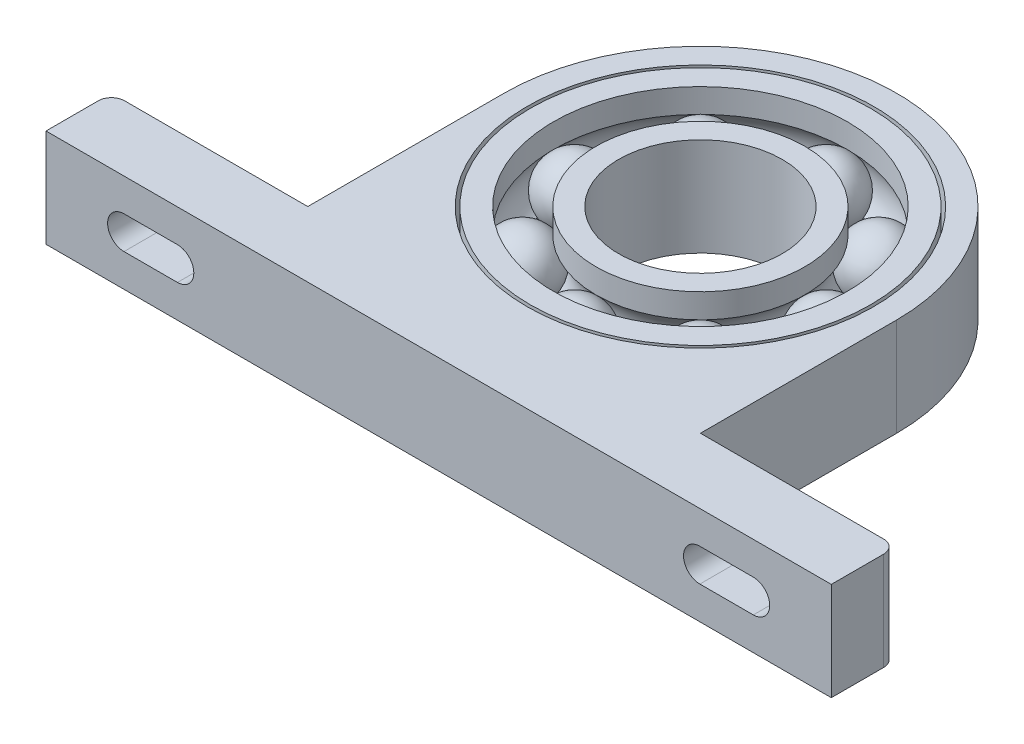
SolidWorks part; units mm, degrees
ref_plane "Front Plane" through (0, 0, 0) normal (0, 0, 1) x (1, 0, 0)
ref_plane "Top Plane" through (0, 0, 0) normal (0, 1, 0) x (1, 0, 0)
ref_plane "Right Plane" through (0, 0, 0) normal (1, 0, 0) x (0, 0, -1)
sketch "Sketch1" plane through (0, 0, 0) normal (0, 0, 1) x (1, 0, 0)
  line L0 (-19.2289, -5) -> (-19.2289, 5)
  line L1 (-15.9578, 7.5) -> (-12.5, 7.5)
  line L2 (-15.9578, 7.5) -> (-15.9578, 3.7815)
  line L3 (-15.9578, -7.5) -> (-12.5, -7.5)
  line L4 (-12.5, 7.5) -> (-12.5, -7.5)
  line L5 (-15.9578, 7.5) -> (-12.5, -7.5) construction
  line L6 (-15.9578, -7.5) -> (-12.5, 7.5) construction
  line L7 (-26, 7.5) -> (-22.4578, 7.5)
  line L8 (-26, 7.5) -> (-26, -7.5)
  line L9 (-26, -7.5) -> (-22.4578, -7.5)
  line L10 (-22.4578, 7.5) -> (-22.4578, 3.8176)
  line L11 (-26, 7.5) -> (-22.4578, -7.5) construction
  line L12 (-26, -7.5) -> (-22.4578, 7.5) construction
  line L13 (0, -10.6091) -> (0, 6.8222) construction
  line L15 (-22.4578, -3.8176) -> (-22.4578, -7.5)
  line L16 (-15.9578, -3.7815) -> (-15.9578, -7.5)
  arc A0 (-22.4578, 3.8176) -> (-22.4578, -3.8176) centre (-19.2289, 0) ccw
  arc A1 (-15.9578, -3.7815) -> (-15.9578, 3.7815) centre (-19.2289, 0) ccw
  arc A2 (-22.4578, 3.8176) -> (-22.4578, -3.8176) centre (-19.2289, 0) ccw
  arc A3 (-19.2289, -5) -> (-19.2289, 5) centre (-19.2289, 0) ccw
  point P0 (-14.2289, 0)
  point P5 (-24.2289, 0)
  dimension "D5" = 15
  dimension "D7" = 10
  dimension "D1" = 26
  dimension "D2" = 12.5
  dimension "D6" = 15
revolve "Revolve1" add sketch "Sketch1" angle 360 about L0 region at (-17.1068, 0, 0)
revolve "Revolve3" add sketch "Sketch1<4>" angle 360 about L13 region at (-14.0114, 0, 0) region at (-24.4545, 0, 0)
sketch "Sketch1<4>" plane through (0, 0, 0) normal (0, 0, 1) x (1, 0, 0) same geometry as "Sketch1"
pattern_circular "CirPattern1" count 8 over 360 reverse direction yes of bodies 101
sketch "Sketch5" plane through (0, 0, 0) normal (0, 1, 0) x (1, 0, 0)
  line L0 (30, 0) -> (30, -30)
  line L1 (30, -30) -> (60, -30)
  line L2 (60, -30) -> (60, -40)
  line L3 (60, -40) -> (-60, -40)
  line L4 (-60, -40) -> (-60, -30)
  line L5 (-60, -30) -> (-30, -30)
  line L6 (-30, -30) -> (-30, 0)
  circle A0 centre (0, 0) radius 26.5
  arc A1 (30, 0) -> (-30, 0) centre (0, 0) ccw
  dimension "D1" = 53
extrude "Boss-Extrude2" add sketch "Sketch5" along normal mid plane 15 separate body
fillet "Fillet1" radius 2 2 edges at (60, 0, 30) (-60, 0, 30)
sketch "Sketch6" plane through (0, 0, 30) normal (0, 0, -1) x (-1, 0, 0)
  line L1 (39.9158, 2.5) -> (48.0842, 2.5)
  line L3 (39.9158, -2.5) -> (48.0842, -2.5)
  line L5 (39.9158, 2.5) -> (48.0842, -2.5) construction
  line L6 (39.9158, -2.5) -> (48.0842, 2.5) construction
  line L7 (0, -20.1138) -> (0, 20.2348)
  line L8 (0, 13.7907) -> (0, -27.5815) construction
  line L9 (0, 7.5) -> (0, -7.5) construction
  line L10 (-39.9158, 2.5) -> (-48.0842, 2.5)
  line L11 (-39.9158, -2.5) -> (-48.0842, -2.5)
  arc A0 (39.9158, 2.5) -> (39.9158, -2.5) centre (39.9158, 0) ccw
  arc A1 (48.0842, -2.5) -> (48.0842, 2.5) centre (48.0842, 0) ccw
  arc A2 (-39.9158, 2.5) -> (-39.9158, -2.5) centre (-39.9158, 0) cw
  arc A3 (-48.0842, -2.5) -> (-48.0842, 2.5) centre (-48.0842, 0) cw
  point P0 (44, 0)
  dimension "D1" = 5
extrude "Cut-Extrude1" cut sketch "Sketch6" against normal blind 15 contours L3 A1 L1 A0 | A3 L11 A2 L10 region at (-44, 0, 30) region at (44, 0, 30)
